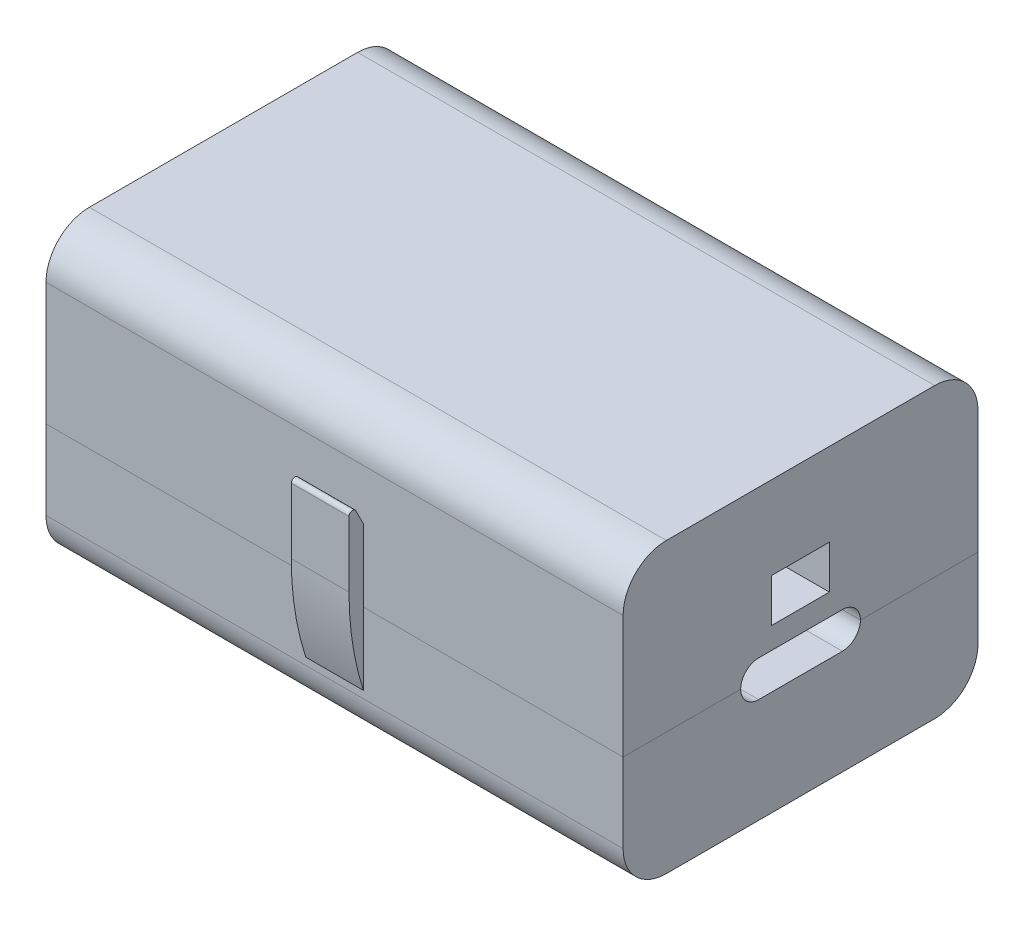
SolidWorks part; units mm, degrees
ref_plane "Front Plane" through (0, 0, 0) normal (0, 0, 1) x (1, 0, 0)
ref_plane "Top Plane" through (0, 0, 0) normal (0, 1, 0) x (1, 0, 0)
ref_plane "Right Plane" through (0, 0, 0) normal (1, 0, 0) x (0, 0, -1)
sketch "Sketch1" plane through (0, 0, 0) normal (0, 1, 0) x (1, 0, 0)
  line L1 (-17, 9.3) -> (17, 9.3)
  line L2 (-17, 9.3) -> (-17, -9.3)
  line L3 (-17, -9.3) -> (17, -9.3)
  line L4 (17, 9.3) -> (17, -9.3)
  line L5 (-17, 9.3) -> (17, -9.3) construction
  line L6 (-17, -9.3) -> (17, 9.3) construction
  line L7 (-20, 12.3) -> (20, 12.3)
  line L8 (-20, 12.3) -> (-20, -12.3)
  line L9 (-20, -12.3) -> (20, -12.3)
  line L10 (20, 12.3) -> (20, -12.3)
  line L11 (-20, 12.3) -> (20, -12.3) construction
  line L12 (-20, -12.3) -> (20, 12.3) construction
  point P0 (0, 0)
  point P6 (0, 0)
  dimension "D1" = 34
  dimension "D2" = 18.6
  dimension "D3" = 3
  dimension "D4" = 3
extrude "Boss-Extrude1" add sketch "Sketch1" along normal blind 14
ref_plane "Plane1" through (0, 5.5, 0) normal (0, -1, 0) x (-1, 0, 0)
sketch "Sketch3" plane through (20, 0, 0) normal (1, 0, 0) x (0, 0, -1)
  line L0 (-13.53, 5.5) -> (13.53, 5.5) construction
  line L1 (-2.9, 5.5) -> (2.9, 5.5) construction
  line L2 (-2.9, 6.75) -> (2.9, 6.75)
  line L3 (-2.9, 4.25) -> (2.9, 4.25)
  line L5 (-4.15, 6.75) -> (4.15, 6.75)
  line L6 (-4.15, 6.75) -> (-4.15, 4.25)
  line L7 (-4.15, 4.25) -> (4.15, 4.25)
  line L8 (4.15, 6.75) -> (4.15, 4.25)
  line L9 (-4.15, 6.75) -> (4.15, 4.25) construction
  line L10 (-4.15, 4.25) -> (4.15, 6.75) construction
  arc A0 (-2.9, 6.75) -> (-2.9, 4.25) centre (-2.9, 5.5) ccw
  arc A1 (2.9, 4.25) -> (2.9, 6.75) centre (2.9, 5.5) ccw
  point P4 (0, 5.5)
  point P9 (0, 5.5)
  dimension "D4" = 1.25
  dimension "D1" = 8.3
  dimension "D2" = 2.5
  dimension "D3" = 0
  dimension "D5" = 0
extrude "Cut-Extrude1" cut sketch "Sketch3" against normal blind 10 contours A1 L2 A0 L3 region at (20, 5.5, 0)
split "Split1" trim tools "Plane1" bodies to split 102 resulting bodies 103 104
sketch "Sketch5" plane through (20, 0, 0) normal (1, 0, 0) x (0, 0, -1)
  line L0 (-2.9, 6.75) -> (2.9, 6.75) construction
  line L1 (-2, 11.25) -> (2, 11.25)
  line L2 (-2, 11.25) -> (-2, 8.25)
  line L3 (-2, 8.25) -> (2, 8.25)
  line L4 (2, 11.25) -> (2, 8.25)
  line L5 (-2, 11.25) -> (2, 8.25) construction
  line L6 (-2, 8.25) -> (2, 11.25) construction
  point P0 (0, 9.75)
  dimension "D1" = 3
  dimension "D2" = 4
  dimension "D3" = 0
  dimension "D4" = 1.5
extrude "Cut-Extrude2" cut sketch "Sketch5" against normal blind 10
sketch "Sketch6" plane through (20, 0, 0) normal (1, 0, 0) x (0, 0, -1)
  line L0 (-12.3, 14) -> (12.3, 14) construction
  line L1 (-9.3, 17) -> (9.3, 17)
  line L2 (-12.3, 14) -> (12.3, 14)
  arc A0 (-12.3, 14) -> (-9.3, 17) centre (-9.3, 14) cw
  arc A1 (12.3, 14) -> (9.3, 17) centre (9.3, 14) ccw
  dimension "D3" = 3
  dimension "D1" = 3
  dimension "D2" = 3
extrude "Boss-Extrude2" add sketch "Sketch6" against normal blind 40 contours L1 A1 L2 A0
sketch "Sketch7" plane through (-20, 0, 0) normal (-1, 0, 0) x (0, 0, 1)
  line L0 (-12.3, 0) -> (12.3, 0) construction
  line L1 (12.3, 5.5) -> (12.3, 0) construction
  line L2 (-12.3, 5.5) -> (-12.3, 0) construction
  line L3 (-9.3, -3) -> (9.3, -3)
  line L4 (12.3, 0) -> (-12.3, 0)
  arc A0 (-12.3, 0) -> (-9.3, -3) centre (-9.3, 0) ccw
  arc A1 (12.3, 0) -> (9.3, -3) centre (9.3, 0) cw
  dimension "D1" = 3
  dimension "D2" = 3
  dimension "D3" = 0
  dimension "D4" = 0
extrude "Boss-Extrude3" add sketch "Sketch7" against normal blind 40
sketch "Sketch8" plane through (0, 0, 12.3) normal (0, 0, 1) x (1, 0, 0)
  line L1 (2, 0.5) -> (-2, 0.5)
  line L2 (2, 0.5) -> (2, 12.5)
  line L3 (2, 12.5) -> (-2, 12.5)
  line L4 (-2, 0.5) -> (-2, 12.5)
  line L5 (2, 0.5) -> (-2, 12.5) construction
  line L6 (2, 12.5) -> (-2, 0.5) construction
  line L7 (20, 5.5) -> (-20, 5.5) construction
  point P0 (0, 6.5)
  point P7 (0, 5.5)
  point P8 (0, 0)
  dimension "D1" = 4
  dimension "D2" = 12
  dimension "D3" = 5
extrude "Boss-Extrude4" add sketch "Sketch8" along normal blind 1
fillet "Fillet4" radius 21 1 edges at (0, 0.5, 13.3)
sketch "Sketch10" plane through (0, 0, 12.3) normal (0, 0, -1) x (-1, 0, 0)
  line L0 (2, 12.5) -> (2, 5.5) construction
  line L1 (-2, 10.5) -> (2, 10.5)
  line L2 (-2, 10.5) -> (-2, 8.5)
  line L3 (-2, 8.5) -> (2, 8.5)
  line L4 (2, 10.5) -> (2, 8.5)
  line L5 (-2, 10.5) -> (2, 8.5) construction
  line L6 (-2, 8.5) -> (2, 10.5) construction
  line L8 (-2, 12.5) -> (2, 12.5) construction
  point P0 (0, 9.5)
  dimension "D1" = 2
  dimension "D2" = 2
extrude "Boss-Extrude6" add sketch "Sketch10" along normal blind 1
sketch "Sketch13" plane through (0, 0, -12.3) normal (0, 0, -1) x (-1, 0, 0)
  line L0 (20, 5.5) -> (-20, 5.5) construction
  line L1 (-13, 5.5) -> (-11, 5.5)
  line L2 (-13, 5.5) -> (-13, 8.5)
  line L3 (-13, 8.5) -> (-11, 8.5)
  line L4 (-11, 5.5) -> (-11, 8.5)
  line L5 (0, 0) -> (0, -9.2638) construction
  line L6 (11, 5.5) -> (11, 8.5)
  line L7 (13, 8.5) -> (11, 8.5)
  line L8 (13, 5.5) -> (13, 8.5)
  line L9 (13, 5.5) -> (11, 5.5)
  line L10 (-20, 5.5) -> (-20, 0) construction
  dimension "D1" = 3
  dimension "D2" = 2
  dimension "D3" = 7
extrude "Boss-Extrude7" add sketch "Sketch13" against normal blind 1
sketch "Sketch14" plane through (0, 0, -11.3) normal (0, 0, 1) x (1, 0, 0)
  line L0 (-11, 8.5) -> (-11, 5.5) construction
  line L1 (-13, 8.5) -> (-11, 8.5)
  line L2 (-13, 8.5) -> (-13, 7)
  line L3 (-13, 7) -> (-11, 7)
  line L4 (-11, 8.5) -> (-11, 7)
  line L5 (13, 8.5) -> (13, 5.5) construction
  line L6 (11, 8.5) -> (13, 8.5)
  line L7 (11, 8.5) -> (11, 7)
  line L8 (11, 7) -> (13, 7)
  line L9 (13, 8.5) -> (13, 7)
  dimension "D1" = 1.5
  dimension "D2" = 1.5
extrude "Boss-Extrude9" add sketch "Sketch14" along normal blind 1 contours L8 L9 L6 L7
extrude "Boss-Extrude10" add sketch "Sketch14<4>" along normal blind 1
sketch "Sketch14<4>" plane through (0, 0, -11.3) normal (0, 0, 1) x (1, 0, 0) same geometry as "Sketch14"
sketch "Sketch15" plane through (13, 0, 0) normal (1, 0, 0) x (0, 0, -1)
  line L0 (10.3, 7) -> (11.3, 8.5)
  line L1 (10.3, 8.5) -> (12.3, 8.5) construction
  line L2 (11.3, 8.5) -> (10.3, 8.5)
  line L3 (10.3, 8.5) -> (10.3, 7)
extrude "Cut-Extrude5" cut sketch "Sketch15" against normal blind 28
sketch "Sketch16" plane through (2, 0, 0) normal (1, 0, 0) x (0, 0, -1)
  line L0 (-13.3, 12.5) -> (-12.3, 10.5)
  line L1 (-12.3, 10.5) -> (-12.3, 12.5)
  line L2 (-12.3, 12.5) -> (-13.3, 12.5)
extrude "Cut-Extrude6" cut sketch "Sketch16" against normal blind 28
fillet "Fillet7" radius 0.25 1 edges at (0, 12.5, 13.3)
sketch "Sketch18" plane through (0, 0, 0) normal (0, 1, 0) x (1, 0, 0)
  line L1 (-17, 9.3) -> (17, 9.3)
  line L2 (-17, 9.3) -> (-17, -9.3)
  line L3 (-17, -9.3) -> (17, -9.3)
  line L4 (17, 9.3) -> (17, -9.3)
extrude "Boss-Extrude11" add sketch "Sketch18" along normal blind 1.25
sketch "Sketch19" plane through (-2, 0, 0) normal (-1, 0, 0) x (0, 0, 1)
  line L0 (12.3, 10.5) -> (11.3, 8.5)
  line L1 (11.3, 8.5) -> (11.3, 10.5)
  line L2 (11.3, 10.5) -> (12.3, 10.5)
extrude "Cut-Extrude7" cut sketch "Sketch19" against normal blind 5.25
